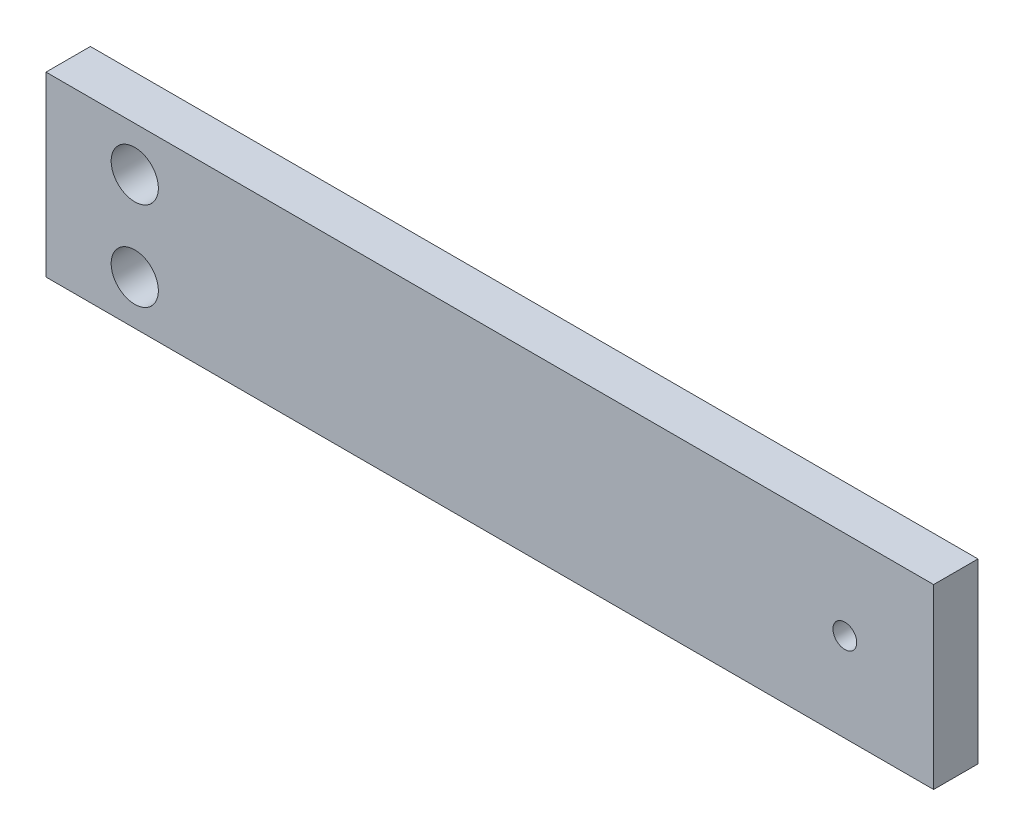
SolidWorks part; units mm, degrees
ref_plane "Front Plane" through (0, 0, 0) normal (0, 0, 1) x (1, 0, 0)
ref_plane "Top Plane" through (0, 0, 0) normal (0, 1, 0) x (1, 0, 0)
ref_plane "Right Plane" through (0, 0, 0) normal (1, 0, 0) x (0, 0, -1)
sketch "Sketch1" plane through (0, 0, 0) normal (0, 0, 1) x (1, 0, 0)
  line L1 (0, 0) -> (127, 0)
  line L2 (0, 0) -> (0, 25.4)
  line L3 (0, 25.4) -> (127, 25.4)
  line L4 (127, 0) -> (127, 25.4)
  dimension "D1" = 25.4
  dimension "D2" = 127
extrude "Boss-Extrude1" add sketch "Sketch1" along normal blind 6.35
sketch "Sketch2" plane through (0, 0, 6.35) normal (0, 0, 1) x (1, 0, 0)
  line L0 (12.7, 25.4) -> (12.7, 0) construction
  line L1 (127, 25.4) -> (0, 25.4) construction
  line L2 (0, 0) -> (127, 0) construction
  line L3 (0, 25.4) -> (0, 0) construction
  point P8 (12.7, 19.05)
  point P9 (12.7, 6.35)
  dimension "D1" = 12.7
  dimension "D2" = 6.35
  dimension "D3" = 6.35
hole_wizard "1/4 Clearance Hole1" positions "Sketch2" profile "Sketch3" hole size "1/4" standard "ANSI Inch" end condition through all
sketch "Sketch3" plane through (12.7, 6.35, 6.35) normal (1, 0, 0) x (0, -1, 0)
  line L0 (0, 0) -> (0, 6.35)
  line L1 (0, 6.35) -> (3.3782, 6.35)
  line L2 (3.3782, 6.35) -> (3.3782, 0)
  line L5 (3.3782, 0) -> (0, 0)
  line L11 (0, -6.35) -> (0, 107.95) construction
  dimension "Thru Hole Dia." = 6.7564
  dimension "Thru Hole Depth" = 6.35
sketch "Sketch4" plane through (0, 0, 6.35) normal (0, 0, 1) x (1, 0, 0)
  line L0 (127, 12.7) -> (114.3, 12.7) construction
  line L1 (127, 0) -> (127, 25.4) construction
  point P1 (114.3, 12.7)
  dimension "D1" = 12.7
hole_wizard "M3 Clearance Hole1" positions "Sketch4" profile "Sketch5" hole size "M3" standard "ANSI Metric" end condition through all
sketch "Sketch5" plane through (114.3, 12.7, 6.35) normal (1, 0, 0) x (0, -1, 0)
  line L0 (0, 0) -> (0, 6.35)
  line L1 (0, 6.35) -> (1.7, 6.35)
  line L2 (1.7, 6.35) -> (1.7, 0)
  line L5 (1.7, 0) -> (0, 0)
  line L11 (0, -6.35) -> (0, 107.95) construction
  dimension "Thru Hole Dia." = 3.4
  dimension "Thru Hole Depth" = 6.35
